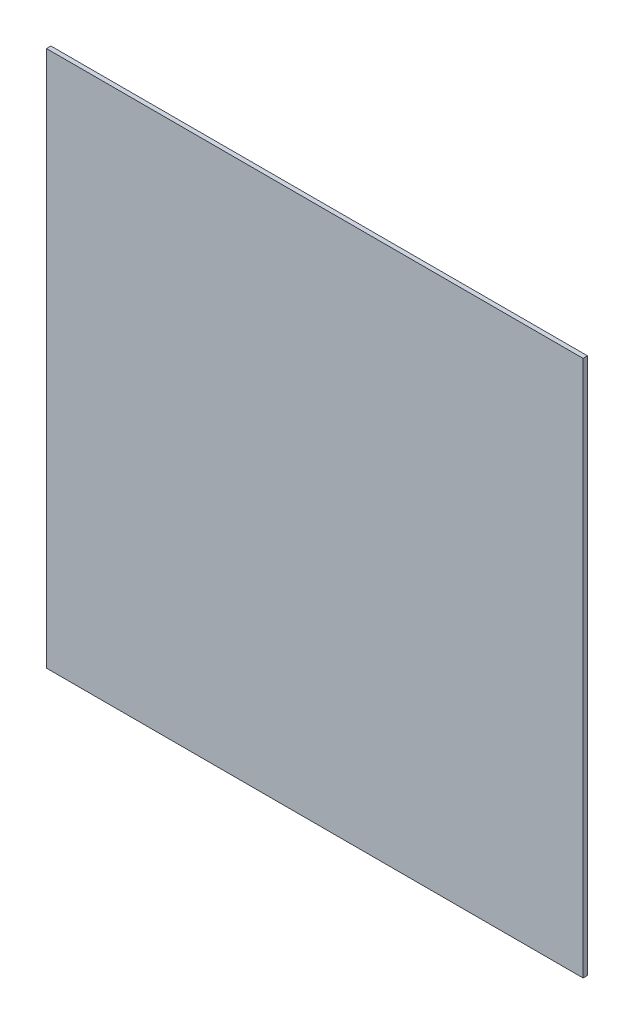
SolidWorks part; units mm, degrees
ref_plane "Front Plane" through (0, 0, 0) normal (0, 0, 1) x (1, 0, 0)
ref_plane "Top Plane" through (0, 0, 0) normal (0, 1, 0) x (1, 0, 0)
ref_plane "Right Plane" through (0, 0, 0) normal (1, 0, 0) x (0, 0, -1)
sketch "Sketch1" plane through (0, 0, 0) normal (0, 0, 1) x (1, 0, 0)
  line L1 (173, 396.7) -> (-227, 396.7)
  line L2 (173, 396.7) -> (173, -3.3)
  line L3 (173, -3.3) -> (-227, -3.3)
  line L4 (-227, 396.7) -> (-227, -3.3)
  line L5 (173, 396.7) -> (-227, -3.3) construction
  line L6 (173, -3.3) -> (-227, 396.7) construction
  point P4 (-27, 196.7)
extrude "Boss-Extrude1" add sketch "Sketch1" along normal blind 3.3
